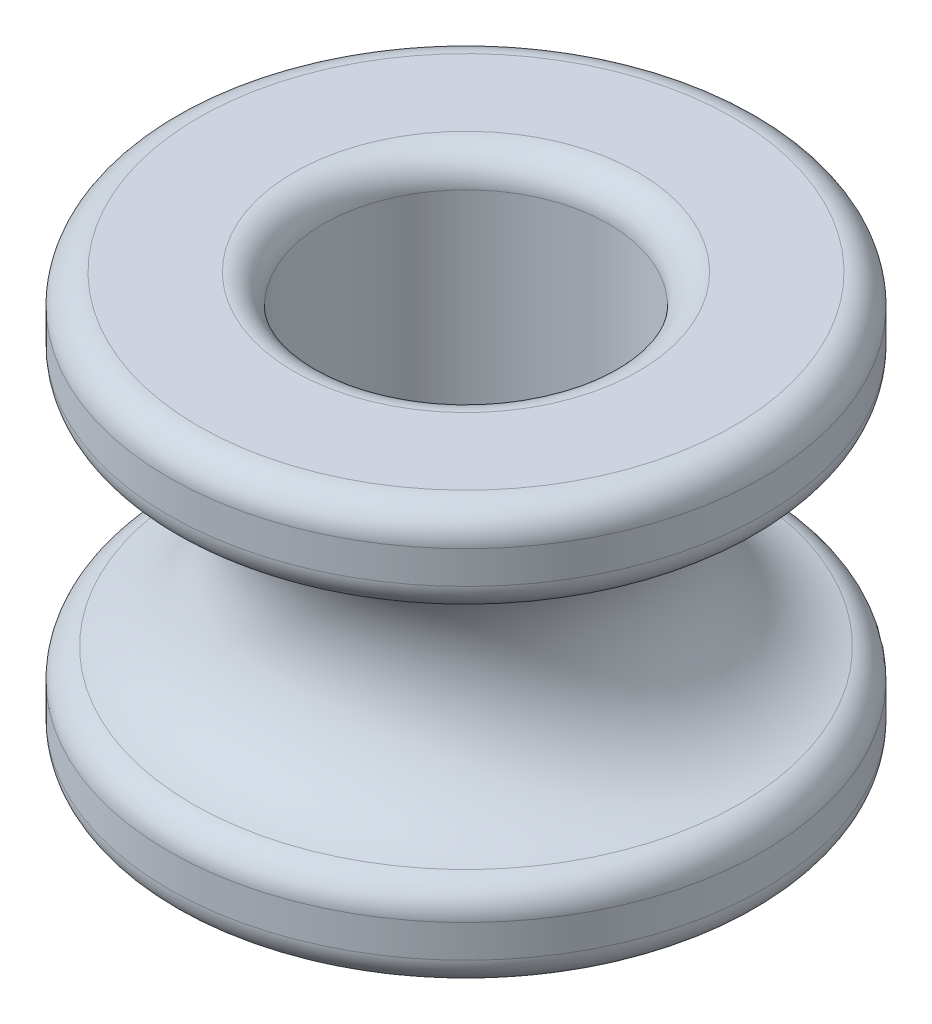
SolidWorks part; units mm, degrees
ref_plane "Front Plane" through (0, 0, 0) normal (0, 0, 1) x (1, 0, 0)
ref_plane "Top Plane" through (0, 0, 0) normal (0, 1, 0) x (1, 0, 0)
ref_plane "Right Plane" through (0, 0, 0) normal (1, 0, 0) x (0, 0, -1)
sketch "Sketch1" plane through (0, 0, 0) normal (0, 0, 1) x (1, 0, 0)
  line L0 (-1.2, 0) -> (3.8, 0) construction
  line L1 (-1.2, -3.5) -> (1.2, -3.5) construction
  line L2 (-1.2, -3.5) -> (-1.2, 3.5) construction
  line L3 (-1.2, 3.5) -> (1.2, 3.5) construction
  line L4 (1.2, -3.5) -> (1.2, 3.5)
  line L5 (-1.2, -3.5) -> (1.2, 3.5) construction
  line L6 (-1.2, 3.5) -> (1.2, -3.5) construction
  line L7 (3.8, 3.5) -> (3.8, -3.5) construction
  line L8 (1.2, 3.5) -> (3.8, 3.5)
  line L9 (1.2, 3.5) -> (1.2, -3.5)
  line L10 (1.2, -3.5) -> (3.8, -3.5)
  line L11 (3.8, 3.5) -> (3.8, 2)
  line L12 (3.8, -2) -> (3.8, -3.5)
  circle A0 centre (3.8, 0) radius 2
  point P0 (0, 0)
  dimension "D1" = 2.4
  dimension "D2" = 7
  dimension "D3" = 5
revolve "Revolve1" add sketch "Sketch1" angle 360 about L2 region at (1.2747, 0, 0)
fillet "Fillet1" radius 0.5 6 edges at (-1.2, -3.5, -2.4) (-1.2, -3.5, -5) (-1.2, -2, -5) (-1.2, 3.5, -2.4) (-1.2, 3.5, -5) (-1.2, 2, -5)
